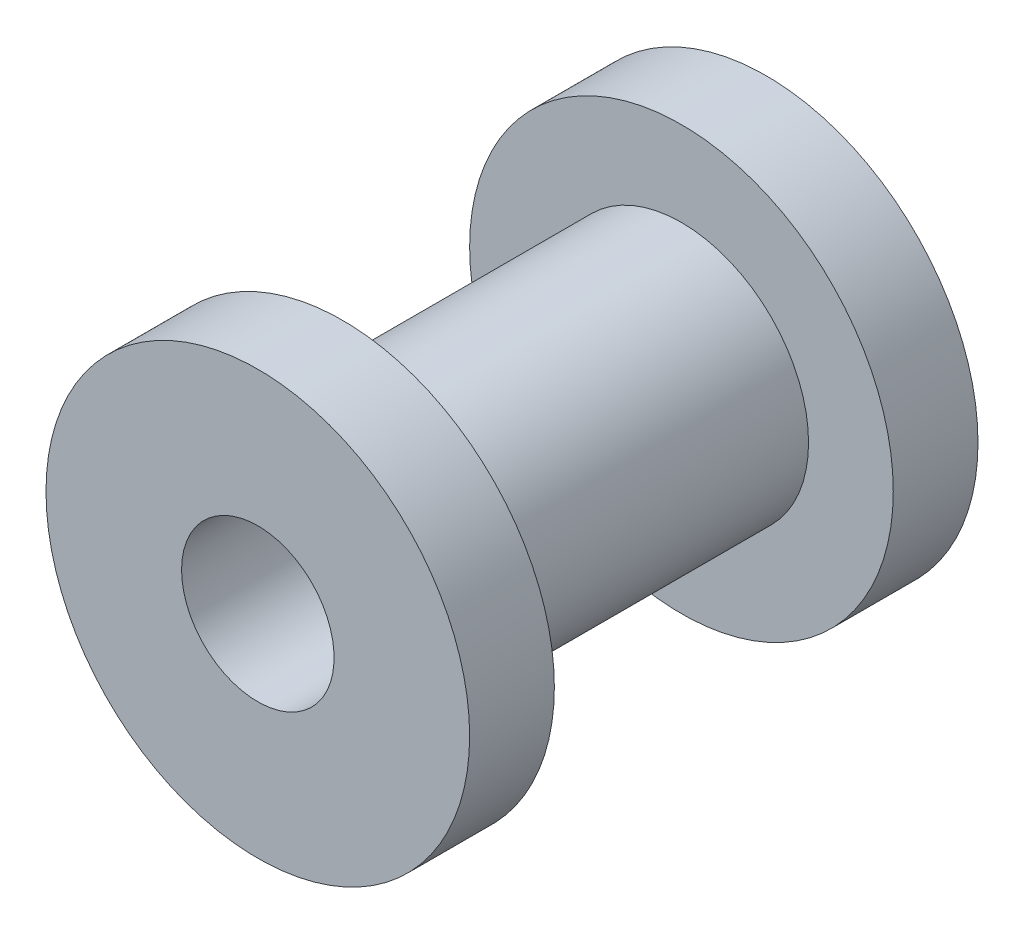
SolidWorks part; units mm, degrees
ref_plane "Front Plane" through (0, 0, 0) normal (0, 0, 1) x (1, 0, 0)
ref_plane "Top Plane" through (0, 0, 0) normal (0, 1, 0) x (1, 0, 0)
ref_plane "Right Plane" through (0, 0, 0) normal (1, 0, 0) x (0, 0, -1)
sketch "Sketch1" plane through (0, 0, 0) normal (0, 0, 1) x (1, 0, 0)
  circle A0 centre (0, 0) radius 9.525
  dimension "D1" = 19.05
extrude "Boss-Extrude1" add sketch "Sketch1" along normal blind 25.4
sketch "Sketch2" plane through (0, 0, 25.4) normal (0, 0, 1) x (1, 0, 0)
  circle A0 centre (0, 0) radius 15.875
  dimension "D1" = 31.75
extrude "Boss-Extrude2" add sketch "Sketch2" along normal blind 6.35
sketch "Sketch3" plane through (0, 0, 0) normal (0, 0, -1) x (-1, 0, 0)
  circle A0 centre (0, 0) radius 15.875
  dimension "D1" = 31.75
extrude "Boss-Extrude3" add sketch "Sketch3" along normal blind 6.35
sketch "Sketch4" plane through (0, 0, -6.35) normal (0, 0, -1) x (-1, 0, 0)
  circle A0 centre (0, 0) radius 5.715
  dimension "D1" = 11.43
extrude "Cut-Extrude1" cut sketch "Sketch4" against normal through all
